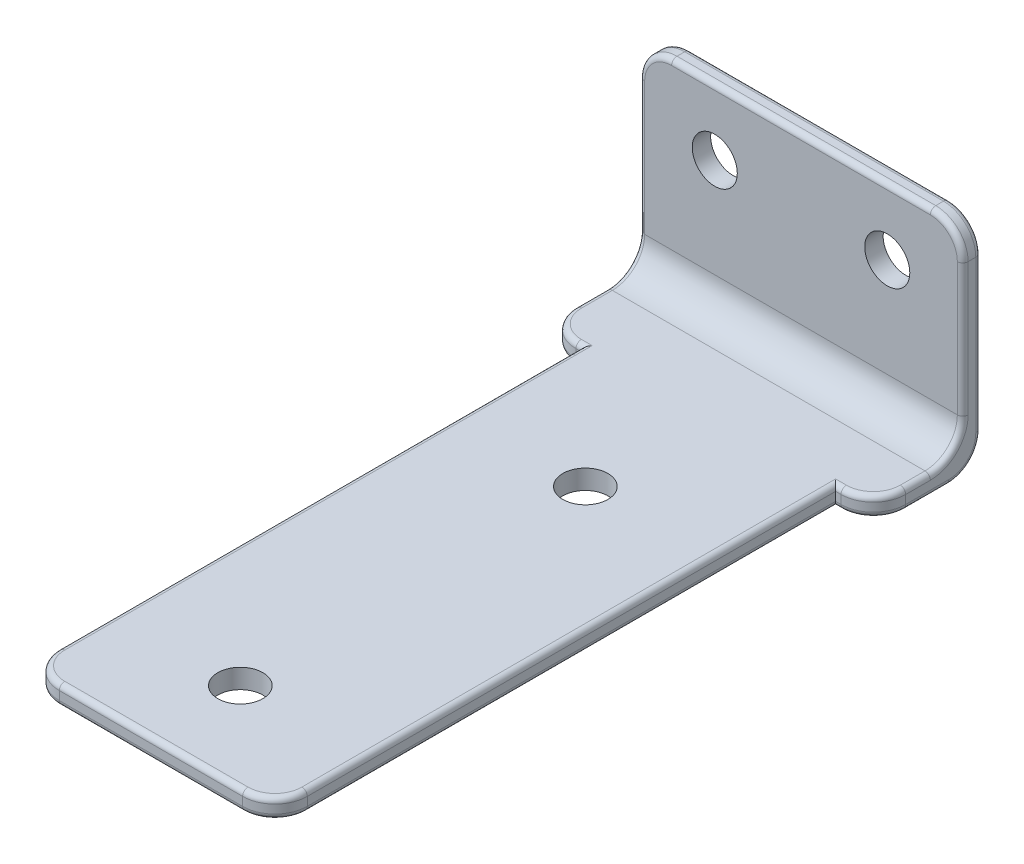
SolidWorks part; units mm, degrees
ref_plane "Front Plane" through (0, 0, 0) normal (0, 0, 1) x (1, 0, 0)
ref_plane "Top Plane" through (0, 0, 0) normal (0, 1, 0) x (1, 0, 0)
ref_plane "Right Plane" through (0, 0, 0) normal (1, 0, 0) x (0, 0, -1)
sketch "Sketch1" plane through (0, 0, 0) normal (0, 1, 0) x (1, 0, 0)
  line L1 (19.05, -39.37) -> (-19.05, -39.37)
  line L2 (19.05, -39.37) -> (19.05, 39.37)
  line L3 (19.05, 39.37) -> (-19.05, 39.37)
  line L4 (-19.05, -39.37) -> (-19.05, 39.37)
  line L5 (19.05, -39.37) -> (-19.05, 39.37) construction
  line L6 (19.05, 39.37) -> (-19.05, -39.37) construction
  point P0 (0, 0)
  dimension "D1" = 78.74
  dimension "D2" = 38.1
extrude "Boss-Base" add sketch "Sketch1" along normal blind 2.286
sketch "Sketch3" plane through (0, 2.286, 0) normal (0, 1, 0) x (1, 0, 0)
  line L0 (19.05, -39.37) -> (19.05, 39.37) construction
  line L1 (-19.05, 39.37) -> (19.05, 39.37)
  line L2 (-19.05, 39.37) -> (-19.05, 37.1983)
  line L3 (-19.05, 37.1983) -> (19.05, 37.1983)
  line L4 (19.05, 39.37) -> (19.05, 37.1983)
  dimension "D1" = 2.1717
extrude "Boss-Lip" add sketch "Sketch3" along normal blind 23.2512
sketch "Base Centerline" plane through (0, 2.286, 0) normal (0, 1, 0) x (1, 0, 0)
  line L0 (0, -39.37) -> (0, 39.37) construction
  line L1 (-19.05, -39.37) -> (19.05, -39.37) construction
  line L2 (19.05, 39.37) -> (-19.05, 39.37) construction
  line L4 (-19.05, 37.1983) -> (19.05, 37.1983) construction
  point P6 (0, -28.8417)
  point P7 (0, 11.7983)
  dimension "D1" = 40.64
  dimension "D2" = 25.4
hole_wizard "#4 (0.209) Diameter Hole1" positions "Sketch5" profile "Sketch6" hole size "#4" standard "ANSI Inch" end condition through all
sketch "Sketch5" plane through (0, 2.286, 0) normal (0, 1, 0) x (1, 0, 0)
  point P0 (0, -28.8417)
  point P3 (0, 11.7983)
sketch "Sketch6" plane through (0, 2.286, 28.8417) normal (1, 0, 0) x (0, 0, 1)
  line L0 (0, 0) -> (0, 2.286)
  line L1 (0, 2.286) -> (2.6543, 2.286)
  line L2 (2.6543, 2.286) -> (2.6543, 0)
  line L5 (2.6543, 0) -> (0, 0)
  line L11 (0, -6.35) -> (0, 107.95) construction
  dimension "Thru Hole Dia." = 5.3086
  dimension "Thru Hole Depth" = 2.286
sketch "Sketch7" plane through (0, 0, -37.1983) normal (0, 0, 1) x (1, 0, 0)
  line L1 (-19.05, 25.5372) -> (-19.05, 2.286) construction
  line L2 (19.05, 25.5372) -> (19.05, 2.286) construction
  line L3 (19.05, 0) -> (-19.05, 0) construction
  point P0 (10.16, 17.78)
  point P1 (-10.16, 17.78)
  dimension "D1" = 17.78
  dimension "D2" = 8.89
  dimension "D3" = 17.78
  dimension "D4" = 8.89
hole_wizard "#4 (0.209) Diameter Hole2" positions "Sketch7" profile "Sketch8" hole size "#4" standard "ANSI Inch" end condition through all
sketch "Sketch8" plane through (10.16, 17.78, -37.1983) normal (1, 0, 0) x (0, -1, 0)
  line L0 (0, 0) -> (0, 2.1717)
  line L1 (0, 2.1717) -> (2.6543, 2.1717)
  line L2 (2.6543, 2.1717) -> (2.6543, 0)
  line L5 (2.6543, 0) -> (0, 0)
  line L11 (0, -6.35) -> (0, 107.95) construction
  dimension "Thru Hole Dia." = 5.3086
  dimension "Thru Hole Depth" = 2.1717
sketch "Sketch19" plane through (0, 2.286, 0) normal (0, 1, 0) x (1, 0, 0)
  line L0 (0, 39.37) -> (0, -39.37) construction
  line L1 (19.05, -39.37) -> (14.605, -39.37)
  line L2 (19.05, -39.37) -> (19.05, 26.67)
  line L3 (19.05, 26.67) -> (14.605, 26.67)
  line L4 (14.605, -39.37) -> (14.605, 26.67)
  line L6 (-19.05, -39.37) -> (-14.605, -39.37)
  line L7 (-19.05, -39.37) -> (-19.05, 25.9334)
  line L8 (-19.05, 25.9334) -> (-14.605, 25.9334)
  line L9 (-14.605, -39.37) -> (-14.605, 25.9334)
  dimension "D1" = 4.445
  dimension "D2" = 66.04
  dimension "D3" = 4.445
extrude "Cut-Extrude1" cut sketch "Sketch19" against normal through all
fillet "Fillet1" radius 3.81 8 edges at (-19.05, 1.143, -25.9334) (19.05, 1.143, -26.67) (14.605, 1.143, 39.37) (-14.605, 1.143, 39.37) (-19.05, 25.5372, -38.2842) (19.05, 25.5372, -38.2842) (0, 0, -39.37) (0, 2.286, -37.1983)
fillet "Fillet4" radius 0.635 36 edges at (17.9341, 24.4212, -37.1983) (-17.9341, 24.4212, -37.1983) (17.9341, 24.4212, -39.37) (-17.9341, 24.4212, -39.37) (13.4891, 0, 38.2541) (-13.4891, 0, 38.2541) (13.4891, 2.286, 38.2541) (-13.4891, 2.286, 38.2541) (19.05, 13.9116, -37.1983) (19.05, 12.7686, -39.37) (0, 25.5372, -37.1983) (0, 25.5372, -39.37) (-19.05, 13.9116, -37.1983) (-19.05, 12.7686, -39.37) (0, 0, 39.37) (0, 2.286, 39.37) (14.605, 0, 4.445) (14.605, 2.286, 4.445) (-14.605, 0, 4.8133) (-14.605, 2.286, 4.8133) (17.9341, 0, -27.7859) (-17.9341, 0, -27.0493) (-17.9341, 2.286, -27.0493) (19.05, 0, -33.02) (-19.05, 0, -32.6517) (-19.05, 2.286, -31.5659) (17.9341, 2.286, -27.7859) (19.05, 2.286, -31.9341) (19.05, 1.1159, -38.2541) (-19.05, 1.1159, -38.2541) (19.05, 3.4019, -36.0824) (-19.05, 3.4019, -36.0824) (14.9225, 2.286, -26.67) (-14.9225, 2.286, -25.9334) (14.9225, 0, -26.67) (-14.9225, 0, -25.9334)
